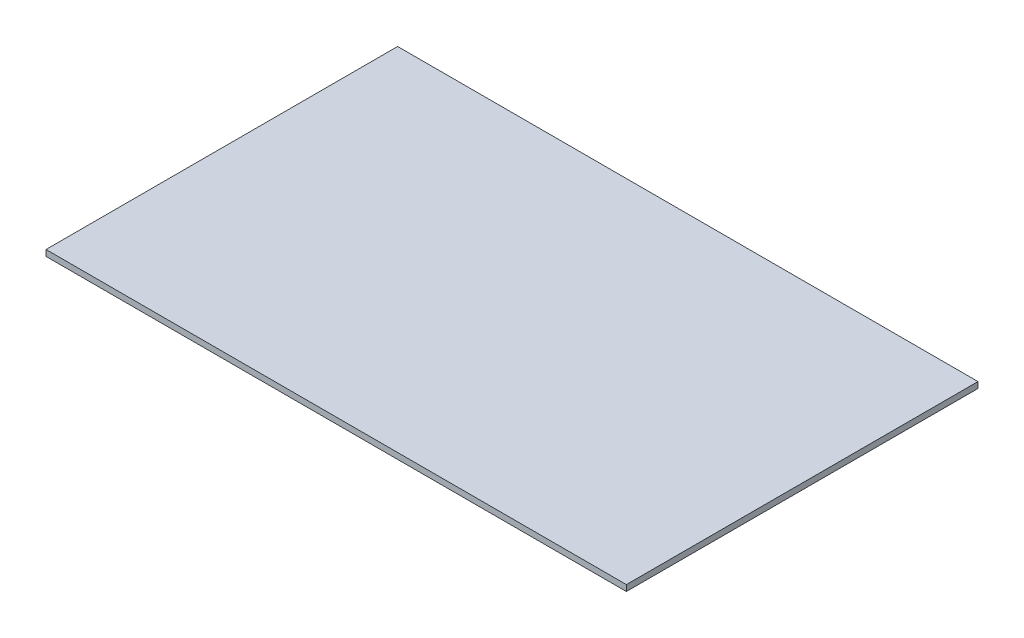
SolidWorks part; units mm, degrees
material "5052-H34"
ref_plane "Front Plane" through (0, 0, 0) normal (0, 0, 1) x (1, 0, 0)
ref_plane "Top Plane" through (0, 0, 0) normal (0, 1, 0) x (1, 0, 0)
ref_plane "Right Plane" through (0, 0, 0) normal (1, 0, 0) x (0, 0, -1)
sketch "Sketch2" plane through (0, 0, 0) normal (0, 0, 1) x (1, 0, 0)
  line L0 (0, 0) -> (458, 0)
  line L1 (0, 0) -> (0, 4.7625)
  line L2 (0, 4.7625) -> (458, 4.7625)
  line L3 (458, 4.7625) -> (458, 0)
extrude "Boss-Extrude1" add sketch "Sketch2" along normal blind 277.48 contours L2 L3 L0 L1
